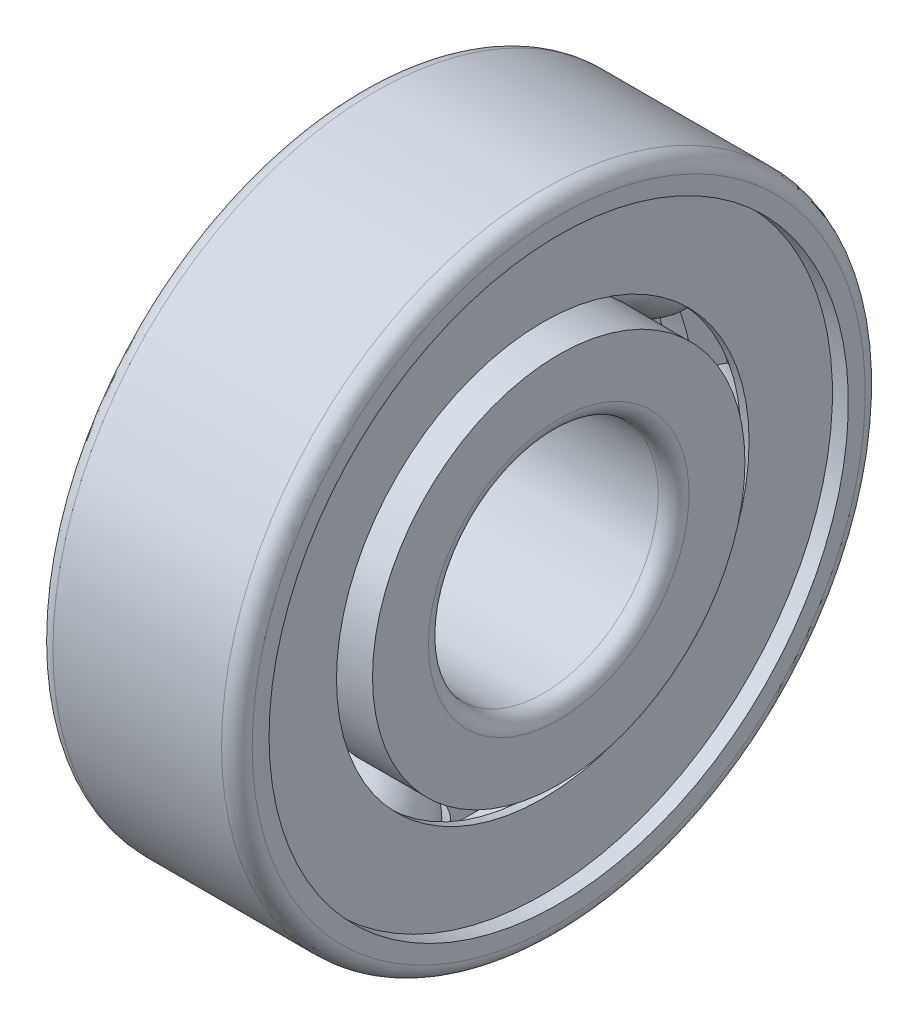
SolidWorks part; units mm, degrees
ref_plane "基准面1" through (0, 0, 0) normal (0, 0, 1) x (1, 0, 0)
ref_plane "基准面2" through (0, 0, 0) normal (0, 1, 0) x (1, 0, 0)
ref_plane "基准面3" through (0, 0, 0) normal (1, 0, 0) x (0, 0, -1)
sketch "尺寸草图" plane through (0, 0, 0) normal (0, 0, 1) x (1, 0, 0)
  point P0 (0, -75.4307)
  point P1 (7.938, -75.4307)
  point P2 (0, 50.7088)
  point P3 (15, 50.7088)
  point P4 (42, 50.7088)
  point P5 (13, 50.7088)
  point P6 (0, -10.9899)
  point P7 (24.3, -10.9899)
  point P8 (36.6, -10.9899)
  point P9 (1, -10.9899)
  point P10 (7, -75.4307)
  dimension "d" = 15
  dimension "DD" = 42
  dimension "B" = 13
  dimension "内圈外径DD2" = 24.3
  dimension "防尘圈径D3" = 36.6
  dimension "r" = 1
  dimension "球径DW" = 7.938
  dimension "球数Z" = 7
sketch "草图2" plane through (0, 0, 0) normal (0, 0, 1) x (1, 0, 0)
  line L0 (-12.4206, 0) -> (9.8128, 0) construction
  line L1 (0, 0) -> (0, 37.3563) construction
  line L2 (-5.5681, 15.525) -> (6.1049, 15.525) construction
  line L3 (-0.8732, 16.6165) -> (0.8732, 16.6165)
  line L4 (-0.8732, 16.6165) -> (-0.8732, 14.4335)
  line L5 (-0.8732, 14.4335) -> (0.8732, 14.4335)
  line L6 (0.8732, 16.6165) -> (0.8732, 14.4335)
  dimension "D1" = 1.7464
  dimension "D2" = 0.8732
  dimension "D3" = 2.1829
  dimension "D4" = 1.0915
  dimension "D5" = 15.525
revolve "基体-旋转" add sketch "草图2" angle 360 about L0
sketch "草图3" plane through (0, 0, 0) normal (0, 0, 1) x (1, 0, 0)
  line L0 (-5.5681, 15.525) -> (6.1049, 15.525) construction
  line L1 (-5.5681, 15.525) -> (6.1049, 15.525) construction
  line L2 (-12.4206, 0) -> (9.8128, 0) construction
  line L3 (-12.4206, 0) -> (9.8128, 0) construction
  line L4 (0, 0) -> (0, 37.3563) construction
  line L5 (0, 0) -> (0, 37.3563) construction
  line L6 (-4.3659, 15.525) -> (4.3659, 15.525)
  arc A0 (-4.3659, 15.525) -> (4.3659, 15.525) centre (0, 15.525) ccw
  dimension "Dwww" = 8.7318
  dimension "D2" = 4.3659
revolve "凸台-旋转1" add sketch "草图3" angle 360 about L1
pattern_circular "阵列(圆周)1" count 7 over 360 about axis through (-12.4206, 0, 0) along (1, 0, 0) of "凸台-旋转1"
sketch "草图4" plane through (0, 0, 0) normal (0, 0, 1) x (1, 0, 0)
  line L0 (0, 0) -> (8.1272, 0) construction
  line L1 (-12.4206, 0) -> (9.8128, 0) construction
  line L3 (-0.8732, 16.6165) -> (0.8732, 16.6165) construction
  line L4 (-4.3659, 20.9824) -> (4.3659, 20.9824)
  line L5 (-4.3659, 20.9824) -> (-4.3659, 16.6165)
  line L6 (-4.3659, 16.6165) -> (4.3659, 16.6165)
  line L7 (4.3659, 20.9824) -> (4.3659, 16.6165)
revolve "切除-旋转1" cut sketch "草图4" angle 360 about L0
sketch "草图5" plane through (0, 0, 0) normal (0, 0, 1) x (1, 0, 0)
  line L0 (0, 0) -> (8.2665, 0) construction
  line L1 (-12.4206, 0) -> (9.8128, 0) construction
  line L2 (-0.8732, 14.4335) -> (0.8732, 14.4335) construction
  line L3 (-4.3659, 14.4335) -> (4.3659, 14.4335)
  line L4 (-4.3659, 14.4335) -> (-4.3659, 10.0676)
  line L5 (-4.3659, 10.0676) -> (4.3659, 10.0676)
  line L6 (4.3659, 14.4335) -> (4.3659, 10.0676)
revolve "切除-旋转2" cut sketch "草图5" angle 360 about L0
sketch "草图6" plane through (0, 0, 0) normal (0, 0, 1) x (1, 0, 0)
  line L0 (0, 0) -> (5.5439, 0) construction
  line L1 (-12.4206, 0) -> (9.8128, 0) construction
  line L2 (0, 0) -> (0, 11.4011) construction
  line L3 (-5.5681, 15.525) -> (6.1049, 15.525) construction
  line L4 (-5.5681, 15.525) -> (6.1049, 15.525) construction
  line L5 (-3.969, 15.525) -> (3.969, 15.525)
  arc A0 (-3.969, 15.525) -> (3.969, 15.525) centre (0, 15.525) ccw
  dimension "Dw" = 7.938
revolve "凸台-旋转2" add sketch "草图6" angle 360 about L4
pattern_circular "阵列(圆周)2" count 7 over 360 about axis through (-12.4206, 0, 0) along (1, 0, 0) of "凸台-旋转2"
sketch "草图7" plane through (0, 0, 0) normal (0, 0, 1) x (1, 0, 0)
  line L0 (0, 0) -> (6.6488, 0) construction
  line L1 (0, 0) -> (0, 16.8954) construction
  line L2 (-5.5, 21) -> (5.5, 21)
  line L3 (-6.5, 20) -> (-6.5, 18.9)
  line L4 (-6.5, 18.9) -> (-2.0696, 18.9)
  line L5 (6.5, 20) -> (6.5, 18.9)
  line L6 (2.0696, 18.9) -> (4.9248, 18.9)
  line L7 (5.46, 18.9) -> (6.5, 18.9)
  line L8 (4.9248, 18.3) -> (5.46, 18.3)
  line L9 (4.9248, 18.3) -> (4.9248, 18.9)
  line L11 (5.46, 18.3) -> (5.46, 18.9)
  arc A0 (-5.5, 21) -> (-6.5, 20) centre (-5.5, 20) ccw
  arc A1 (5.5, 21) -> (6.5, 20) centre (5.5, 20) cw
  arc A2 (3.816, 16.6165) -> (-3.816, 16.6165) centre (0, 15.525) ccw construction
  arc A3 (2.0886, 18.9) -> (-0.0001, 11.556) centre (0, 15.525) ccw construction
  arc A4 (2.0696, 18.9) -> (-2.0696, 18.9) centre (0, 15.525) ccw
  point P10 (-6.5, 21)
  point P13 (6.5, 21)
  dimension "R" = 1
  dimension "D1" = 0.01
  dimension "D2" = 37.8
  dimension "D" = 42
  dimension "D3" = 6.5
  dimension "B" = 13
  dimension "D4" = 0.5352
  dimension "D5" = 36.6
  dimension "D6" = 1.04
revolve "凸台-旋转3" add sketch "草图7" angle 360 about L0
sketch "草图8" plane through (0, 0, 0) normal (0, 0, 1) x (1, 0, 0)
  line L0 (-12.4206, 0) -> (9.8128, 0) construction
  line L1 (-12.4206, 0) -> (9.8128, 0) construction
  line L2 (6.5, 20) -> (6.5, 18.9) construction
  line L3 (-6.5, 12.15) -> (-2.0696, 12.15)
  line L4 (-6.5, 12.15) -> (-6.5, 8.5)
  line L5 (-5.5, 7.5) -> (5.5, 7.5)
  line L6 (6.5, 12.15) -> (6.5, 8.5)
  line L7 (-6.5, 20) -> (-6.5, 18.9) construction
  line L8 (2.0696, 12.15) -> (6.5, 12.15)
  arc A0 (-6.5, 8.5) -> (-5.5, 7.5) centre (-5.5, 8.5) ccw
  arc A1 (5.5, 7.5) -> (6.5, 8.5) centre (5.5, 8.5) ccw
  arc A2 (-3.816, 14.4335) -> (3.816, 14.4335) centre (0, 15.525) ccw construction
  arc A3 (-3.816, 14.4335) -> (3.816, 14.4335) centre (0, 15.525) ccw construction
  arc A4 (-2.0696, 12.15) -> (2.0696, 12.15) centre (0, 15.525) ccw
  dimension "D1" = 1
  dimension "DD" = 15
  dimension "D2" = 0.01
  dimension "DD2" = 24.3
revolve "凸台-旋转4" add sketch "草图8" angle 360 about L1
sketch "草图10" plane through (0, 0, 0) normal (0, 0, 1) x (1, 0, 0)
  line L0 (4.9248, 18.9) -> (4.9248, -18.9) construction
  line L1 (5.46, 18.3) -> (4.9248, 18.3)
  line L2 (5.46, 18.3) -> (5.46, 13.4598)
  line L3 (5.46, 13.4598) -> (4.9248, 13.4598)
  line L4 (4.9248, 18.3) -> (4.9248, 13.4598)
  line L5 (2.0696, 12.15) -> (6.5, 12.15) construction
  line L6 (0, 0) -> (-5.3515, 0) construction
  line L7 (-12.4206, 0) -> (9.8128, 0) construction
  dimension "D1" = 1.3098
revolve "凸台-旋转5" add sketch "草图10" angle 360 about L6
sketch "草图11" plane through (0, 0, 0) normal (1, 0, 0) x (0, 0, -1)
  circle A0 centre (0, 0) radius 21
  circle A1 centre (0, 0) radius 21 construction
extrude "切除-拉伸1" cut sketch "草图11" against normal blind 10
mirror "镜向所有1" about plane through (0, 0, 0) normal (1, 0, 0) of bodies 109
equation "\"D5@草图7\" = \"防尘圈径D3@尺寸草图\""
equation "\"Z@阵列(圆周)1\"=\"球数Z@尺寸草图\" "
equation "\"Dw@草图6\"=\"球径DW@尺寸草图\""
equation "\"DD@草图8\"=\"d@尺寸草图\""
equation "\"D@草图7\"=\"DD@尺寸草图\""
equation "\"B@草图7\"=\"B@尺寸草图\" "
equation "\"DD2@草图8\"=\"内圈外径DD2@尺寸草图\""
equation "\"R@草图7\"=\"r@尺寸草图\""
equation "\"D3@草图2\" = 0.25*\"Dwww@草图3\""
equation "\"D4@草图2\" = \"D3@草图2\"/2"
equation "\"Dwww@草图3\" = 1.1*\"Dw@草图6\""
equation "\"D2@草图3\" = 0.5*\"Dwww@草图3\""
equation "\"D1@草图2\" = 0.2*\"Dwww@草图3\""
equation "\"D2@草图2\" = 0.5*\"D1@草图2\""
equation "\"切除位置@草图4\" = \"Dwww@草图3\"/2"
equation "\"D1@阵列(圆周)2\" = \"Z@阵列(圆周)1\""
equation "\"D3@草图7\" = \"B@草图7\" / 2"
equation "\"D1@草图8\" = \"R@草图7\""
equation "\"D2@草图7\" = 0.9*\"D@草图7\""
equation "\"D5@草图2\" = 0.25* ( \"D2@草图7\" + \"DD2@草图8\" )  "
equation "\"D6@草图7\" = 0.08 * \"B@草图7\""
equation "\"D1@草图10\" = 0.15*\"Dwww@草图3\""
